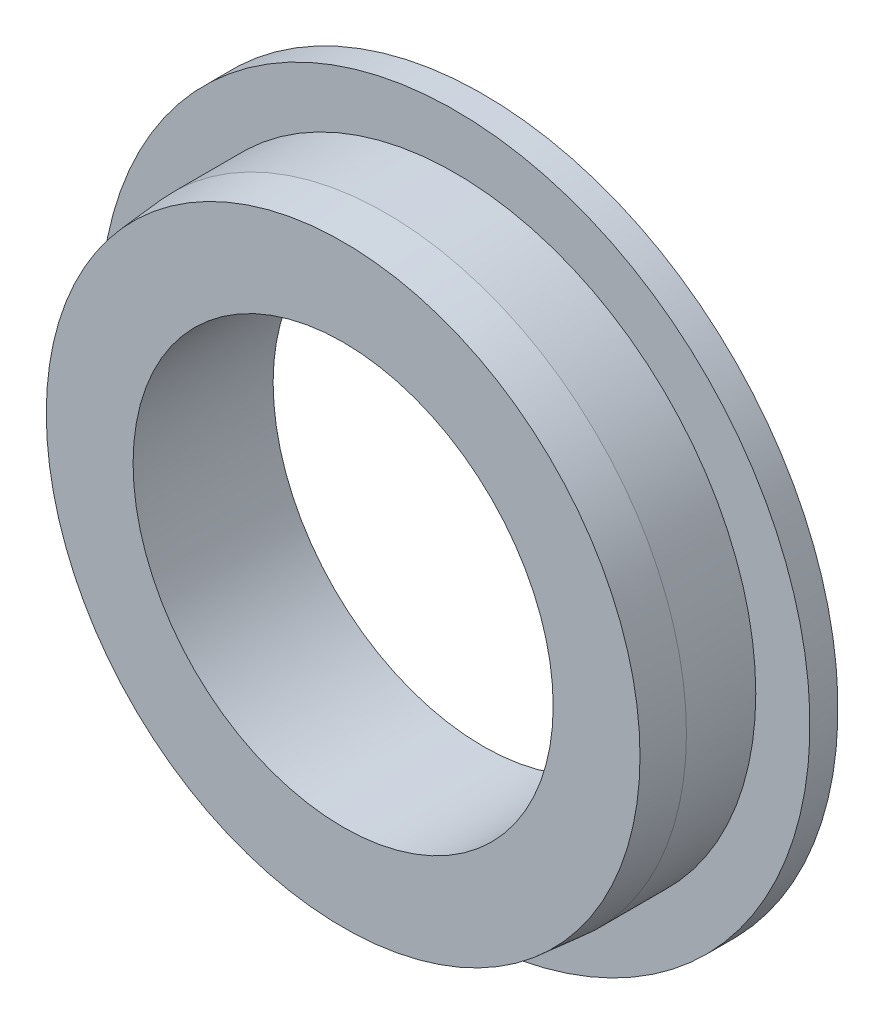
SolidWorks part; units mm, degrees
ref_plane "Front Plane" through (0, 0, 0) normal (0, 0, 1) x (1, 0, 0)
ref_plane "Top Plane" through (0, 0, 0) normal (0, 1, 0) x (1, 0, 0)
ref_plane "Right Plane" through (0, 0, 0) normal (1, 0, 0) x (0, 0, -1)
sketch "Sketch1" plane through (0, 0, 0) normal (0, 0, 1) x (1, 0, 0)
  circle A0 centre (0, 0) radius 24.13
  dimension "D1" = 48.26
extrude "Boss-Extrude1" add sketch "Sketch1" along normal mid plane 1.905
sketch "Sketch2" plane through (0, 0, 0.9525) normal (0, 0, 1) x (1, 0, 0)
  circle A0 centre (0, 0) radius 20.447
  dimension "D1" = 40.894
extrude "Boss-Extrude2" add sketch "Sketch2" along normal blind 7.62
sketch "Sketch4" plane through (0, 0, -0.9525) normal (0, 0, -1) x (-1, 0, 0)
  circle A0 centre (0, 0) radius 14.2875
  dimension "D1" = 28.575
extrude "Cut-Extrude1" cut sketch "Sketch4" against normal through all
chamfer "Chamfer1" distance 0.254 angle 85 1 edges at (20.447, 0, 8.5725) first distance on face at (-14.2875, 0, 8.5725)
